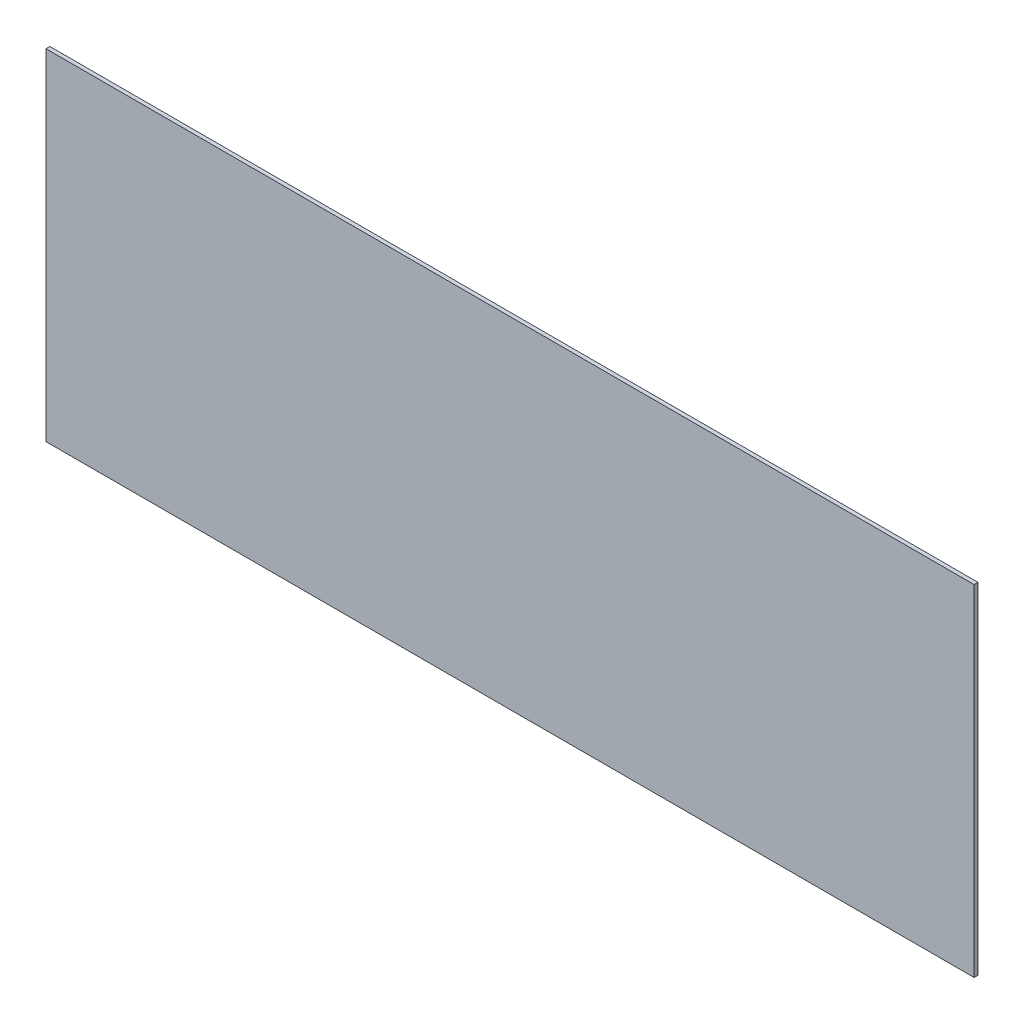
SolidWorks part; units mm, degrees
ref_plane "Front Plane" through (0, 0, 0) normal (0, 0, 1) x (1, 0, 0)
ref_plane "Top Plane" through (0, 0, 0) normal (0, 1, 0) x (1, 0, 0)
ref_plane "Right Plane" through (0, 0, 0) normal (1, 0, 0) x (0, 0, -1)
sketch "Sketch1" plane through (0, 0, 0) normal (0, 0, 1) x (1, 0, 0)
  line L1 (-381, 139.7) -> (381, 139.7)
  line L2 (-381, 139.7) -> (-381, -139.7)
  line L3 (-381, -139.7) -> (381, -139.7)
  line L4 (381, 139.7) -> (381, -139.7)
  line L5 (-381, 139.7) -> (381, -139.7) construction
  line L6 (-381, -139.7) -> (381, 139.7) construction
  point P0 (0, 0)
  dimension "D1" = 762
  dimension "D2" = 279.4
extrude "Boss-Extrude1" add sketch "Sketch1" along normal blind 3.175
